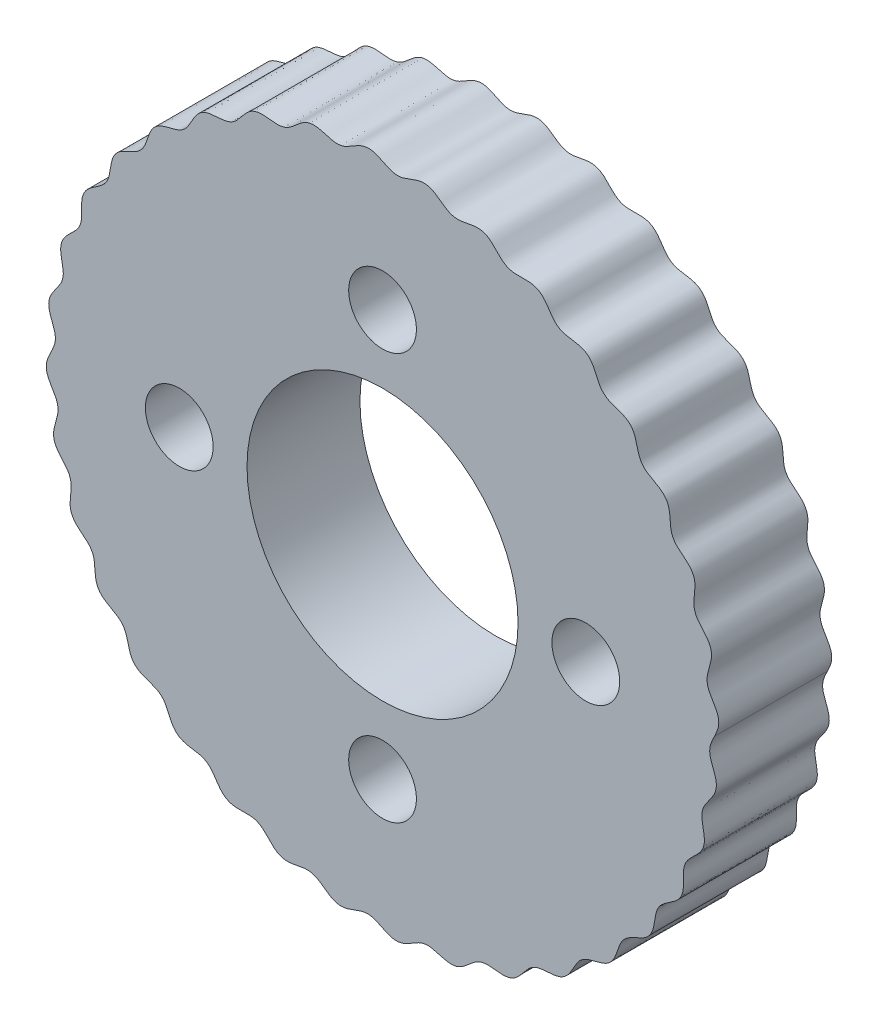
SolidWorks part; units mm, degrees
ref_plane "Front" through (0, 0, 0) normal (0, 0, 1) x (1, 0, 0)
ref_plane "Top" through (0, 0, 0) normal (0, 1, 0) x (1, 0, 0)
ref_plane "Right" through (0, 0, 0) normal (1, 0, 0) x (0, 0, -1)
sketch "草图1" plane through (0, 0, 0) normal (0, 0, 1) x (1, 0, 0)
  circle A0 centre (0, 0) radius 12
  spline S0 degree 4 poles (28.3227, -9.203) (28.4007, -9.0473) (28.5134, -8.7154) (28.521, -8.2566) (28.4217, -7.7169) (28.3239, -7.2476) (28.2639, -6.8452) (28.2638, -6.3709) (28.4238, -5.8514) (28.7631, -5.3537) (29.1643, -4.834) (29.4939, -4.2847) (29.6044, -3.6732) (29.5058, -3.1673) (29.3734, -2.7786) (29.2476, -2.4588) (29.149, -2.2029) (29.0638, -1.9517) (29.0012, -1.7034) (28.9682, -1.4588) (28.9679, -1.2213) (29.0011, -0.9856) (29.0631, -0.7564) (29.1442, -0.5392) (29.2452, -0.3153) (29.3566, -0.0878) (29.4214, 0.0426) (29.5041, 0.2162) (29.5813, 0.3888) (29.6627, 0.5946) (29.7361, 0.8371) (29.7928, 1.1772) (29.7619, 1.5385) (29.6612, 1.8607) (29.5296, 2.143) (29.4093, 2.3613) (29.2811, 2.5748) (29.1513, 2.7874) (29.0136, 3.0244) (28.8805, 3.2922) (28.7417, 3.6812) (28.7105, 4.1623) (28.8201, 4.6646) (28.9806, 5.1874) (29.1102, 5.669) (29.1612, 6.1634) (29.0681, 6.6503) (28.8378, 7.079) (28.5417, 7.4523) (28.2371, 7.7886) (27.9601, 8.1196) (27.7409, 8.4673) (27.607, 8.8339) (27.5577, 9.2505) (27.5832, 9.6969) (27.6437, 10.169) (27.6846, 10.6732) (27.6396, 11.1805) (27.4409, 11.6518) (27.114, 12.0368) (26.734, 12.3591) (26.3695, 12.6411) (26.0523, 12.9227) (25.8058, 13.2224) (25.6414, 13.5328) (25.5328, 13.9054) (25.4814, 14.3267) (25.4592, 14.7869) (25.4154, 15.2832) (25.2947, 15.7655) (25.0405, 16.1911) (24.6776, 16.5153) (24.2715, 16.7647) (23.8703, 16.9765) (23.4969, 17.1929) (23.1719, 17.4446) (22.9207, 17.7433) (22.7319, 18.1179) (22.6032, 18.5461) (22.4985, 19.0105) (22.3646, 19.4982) (22.1488, 19.9595) (21.8008, 20.3344) (21.362, 20.5844) (20.8947, 20.7574) (20.4558, 20.8976) (20.0613, 21.0538) (19.7272, 21.2511) (19.4665, 21.4865) (19.237, 21.7996) (19.0447, 22.1778) (18.8664, 22.6027) (18.6555, 23.0541) (18.3771, 23.466) (17.9927, 23.779) (17.5408, 23.9595) (17.0739, 24.055) (16.6245, 24.1169) (16.1995, 24.1924) (15.8081, 24.3178) (15.4699, 24.5126) (15.1644, 24.8) (14.8969, 25.1584) (14.6397, 25.5589) (14.3471, 25.9715) (13.9865, 26.3312) (13.5313, 26.5645) (13.0334, 26.6493) (12.5351, 26.6519) (12.0747, 26.6336) (11.6507, 26.6454) (11.2692, 26.7166) (10.9437, 26.8487) (10.621, 27.0643) (10.3109, 27.354) (9.998, 27.6922) (9.6455, 28.0444) (9.243, 28.3362) (8.7747, 28.4988) (8.2883, 28.5139) (7.817, 28.4439) (7.3734, 28.3483) (6.9483, 28.274) (6.5375, 28.258) (6.1531, 28.3253) (5.7677, 28.4909) (5.3939, 28.7362) (5.0152, 29.0246) (4.5991, 29.3122) (4.1372, 29.5269) (3.6297, 29.5904) (3.1328, 29.4998) (2.6637, 29.3319) (2.2373, 29.1572) (1.8348, 29.0233) (1.4519, 28.9597) (1.101, 28.9725) (0.7239, 29.0647) (0.3335, 29.2309) (-0.0762, 29.4417) (-0.5279, 29.652) (-1.006, 29.7886) (-1.5017, 29.7812) (-1.9639, 29.629) (-2.3829, 29.4021) (-2.7669, 29.1606) (-3.141, 28.9453) (-3.5215, 28.7898) (-3.9058, 28.7216) (-4.3246, 28.7454) (-4.7598, 28.848) (-5.2143, 28.9895) (-5.7037, 29.1175) (-6.2111, 29.1611) (-6.7098, 29.0473) (-7.1456, 28.7922) (-7.5292, 28.4742) (-7.8698, 28.1637) (-8.2027, 27.901) (-8.6163, 27.6658) (-9.0846, 27.5515) (-9.5983, 27.5723) (-10.141, 27.6395) (-10.6379, 27.6835) (-11.1335, 27.6479) (-11.5969, 27.4717) (-11.9791, 27.1704) (-12.2953, 26.814) (-12.5736, 26.4556) (-12.8515, 26.1254) (-13.1558, 25.8491) (-13.4936, 25.6536) (-13.8953, 25.5327) (-14.3393, 25.4803) (-14.8148, 25.4579) (-15.3184, 25.4107) (-15.8102, 25.2782) (-16.2399, 25.0007) (-16.5622, 24.6119) (-16.8137, 24.1817) (-17.0281, 23.7738) (-17.2503, 23.4125) (-17.5027, 23.1177) (-17.7798, 22.9019) (-18.1279, 22.7302) (-18.5338, 22.6065) (-18.9832, 22.5047) (-19.4644, 22.3754) (-19.9184, 22.1728) (-20.2933, 21.8485) (-20.5496, 21.4348) (-20.7247, 20.9916) (-20.8637, 20.5598) (-21.0118, 20.1544) (-21.2033, 19.7906) (-21.4539, 19.4914) (-21.79, 19.2405) (-22.1893, 19.0393) (-22.6285, 18.8556) (-23.0856, 18.639) (-23.5024, 18.3463) (-23.8112, 17.9386) (-23.9811, 17.463) (-24.0705, 16.9728) (-24.1319, 16.516) (-24.218, 16.1008) (-24.3837, 15.6548) (-24.669, 15.2662) (-25.0758, 14.9519) (-25.5348, 14.6546) (-25.9437, 14.3689) (-26.3005, 14.023) (-26.5422, 13.5902) (-26.6414, 13.1137) (-26.6544, 12.6374) (-26.6373, 12.184) (-26.6379, 11.7525) (-26.6934, 11.3451) (-26.8265, 10.9783) (-27.0565, 10.6275) (-27.363, 10.3019) (-27.7128, 9.9791) (-28.0683, 9.6192) (-28.3598, 9.2016) (-28.5106, 8.7128) (-28.5076, 8.2078) (-28.4239, 7.7167) (-28.3254, 7.2664) (-28.2643, 6.8468) (-28.2674, 6.371) (-28.4026, 5.9083) (-28.6774, 5.4737) (-29.0071, 5.0374) (-29.2934, 4.6291) (-29.5189, 4.1654) (-29.596, 3.6363) (-29.5072, 3.1705) (-29.3741, 2.7812) (-29.2486, 2.4612) (-29.1621, 2.237) (-29.0944, 2.0423) (-29.039, 1.8536) (-28.9969, 1.671) (-28.9683, 1.4602) (-28.9678, 1.2226) (-29.0008, 0.9866) (-29.0628, 0.7571) (-29.144, 0.5397) (-29.2451, 0.3156) (-29.3565, 0.088) (-29.4213, -0.0425) (-29.504, -0.216) (-29.5811, -0.3884) (-29.6625, -0.594) (-29.7359, -0.8363) (-29.7927, -1.1758) (-29.7569, -1.5999) (-29.5968, -2.0358) (-29.3501, -2.468) (-29.104, -2.8573) (-28.9029, -3.23) (-28.7425, -3.6775) (-28.7102, -4.158) (-28.8184, -4.6601) (-28.9796, -5.1824) (-29.108, -5.6634) (-29.1694, -6.219) (-29.0205, -6.8287) (-28.6698, -7.3074) (-28.2995, -7.7184) (-27.9914, -8.0807) (-27.773, -8.4064) (-27.66, -8.6803) (-27.6148, -8.8706) (-27.5993, -8.9677) knots 0 0 0 0 0 0.005917 0.011834 0.015307 0.01878 0.022253 0.025726 0.031361 0.036997 0.042632 0.048268 0.052952 0.057637 0.059979 0.062321 0.064663 0.067005 0.069026 0.071047 0.073068 0.075089 0.07711 0.079131 0.081152 0.083173 0.084644 0.086115 0.087586 0.089057 0.091999 0.094941 0.099192 0.101318 0.103443 0.105569 0.107694 0.10982 0.111945 0.11492 0.117895 0.123845 0.128096 0.132347 0.136598 0.140849 0.14491 0.148972 0.153034 0.157095 0.160395 0.163694 0.166994 0.170293 0.174609 0.178924 0.18324 0.187556 0.191807 0.196057 0.200308 0.204559 0.207534 0.210509 0.213484 0.216459 0.22071 0.224961 0.229212 0.233463 0.237525 0.241586 0.245648 0.24971 0.253009 0.256309 0.259608 0.262908 0.267223 0.271539 0.275854 0.28017 0.284421 0.288672 0.292923 0.297174 0.300149 0.303124 0.306099 0.309073 0.313324 0.317575 0.321826 0.326077 0.330139 0.334201 0.338262 0.342324 0.345623 0.348923 0.352222 0.355522 0.359838 0.364153 0.368469 0.372784 0.377035 0.381286 0.385537 0.389788 0.392763 0.395738 0.398713 0.401688 0.405939 0.41019 0.414441 0.418692 0.422753 0.426815 0.430877 0.434938 0.438238 0.441537 0.444837 0.448136 0.452452 0.456768 0.461083 0.465399 0.46965 0.473901 0.478152 0.482403 0.485378 0.488352 0.491327 0.494302 0.498553 0.502804 0.507055 0.511306 0.515368 0.519429 0.523491 0.527553 0.530852 0.534152 0.537451 0.540751 0.545066 0.549382 0.553698 0.558013 0.562264 0.566515 0.570766 0.575017 0.577992 0.580967 0.586917 0.591168 0.595419 0.59967 0.60392 0.607982 0.612044 0.616105 0.620167 0.623467 0.626766 0.630066 0.633365 0.637681 0.641996 0.646312 0.650628 0.654878 0.659129 0.66338 0.667631 0.670606 0.673581 0.676556 0.679531 0.683782 0.688033 0.692284 0.696535 0.700597 0.704658 0.70872 0.712782 0.716081 0.71938 0.72268 0.725979 0.730295 0.734611 0.738926 0.743242 0.747493 0.751744 0.755995 0.760246 0.763221 0.766196 0.772145 0.776396 0.780647 0.784898 0.789149 0.793211 0.797273 0.801334 0.805396 0.808695 0.811995 0.815294 0.818594 0.822909 0.827225 0.831541 0.835856 0.840107 0.844358 0.848609 0.85286 0.855835 0.85881 0.86476 0.869011 0.873262 0.877513 0.881764 0.886453 0.891141 0.893486 0.89583 0.898175 0.899347 0.900519 0.902542 0.904565 0.906588 0.908611 0.910634 0.912657 0.91468 0.916703 0.918172 0.919642 0.921111 0.922581 0.92552 0.928459 0.932706 0.936953 0.9412 0.945447 0.948419 0.951391 0.957335 0.961582 0.965829 0.970076 0.974323 0.980485 0.986648 0.989986 0.993324 0.996662 1 1 1 1 1 construction
  spline S1 degree 4 poles (29.4, 0) (29.4158, 0.0323) (29.4474, 0.0972) (29.5041, 0.2162) (29.5813, 0.3888) (29.6627, 0.5946) (29.7361, 0.8371) (29.7928, 1.1772) (29.7619, 1.5385) (29.6612, 1.8607) (29.5296, 2.143) (29.4093, 2.3613) (29.2811, 2.5748) (29.1513, 2.7874) (29.0136, 3.0244) (28.8805, 3.2922) (28.7417, 3.6812) (28.7105, 4.1623) (28.8201, 4.6646) (28.9806, 5.1874) (29.1102, 5.669) (29.1612, 6.1634) (29.0681, 6.6503) (28.8378, 7.079) (28.5417, 7.4523) (28.2371, 7.7886) (27.9601, 8.1196) (27.7409, 8.4673) (27.607, 8.8339) (27.5577, 9.2505) (27.5832, 9.6969) (27.6437, 10.169) (27.6846, 10.6732) (27.6396, 11.1805) (27.4409, 11.6518) (27.114, 12.0368) (26.734, 12.3591) (26.3695, 12.6411) (26.0523, 12.9227) (25.8058, 13.2224) (25.6414, 13.5328) (25.5328, 13.9054) (25.4814, 14.3267) (25.4592, 14.7869) (25.4154, 15.2832) (25.2947, 15.7655) (25.0405, 16.1911) (24.6776, 16.5153) (24.2715, 16.7647) (23.8703, 16.9765) (23.4969, 17.1929) (23.1719, 17.4446) (22.9207, 17.7433) (22.7319, 18.1179) (22.6032, 18.5461) (22.4985, 19.0105) (22.3646, 19.4982) (22.1488, 19.9595) (21.8008, 20.3344) (21.362, 20.5844) (20.8947, 20.7574) (20.4558, 20.8976) (20.0613, 21.0538) (19.7272, 21.2511) (19.4665, 21.4865) (19.237, 21.7996) (19.0447, 22.1778) (18.8664, 22.6027) (18.6555, 23.0541) (18.3771, 23.466) (17.9927, 23.779) (17.5408, 23.9595) (17.0739, 24.055) (16.6245, 24.1169) (16.1995, 24.1924) (15.8081, 24.3178) (15.4699, 24.5126) (15.1644, 24.8) (14.8969, 25.1584) (14.6397, 25.5589) (14.3471, 25.9715) (13.9865, 26.3312) (13.5313, 26.5645) (13.0334, 26.6493) (12.5351, 26.6519) (12.0747, 26.6336) (11.6507, 26.6454) (11.2692, 26.7166) (10.9437, 26.8487) (10.621, 27.0643) (10.3109, 27.354) (9.998, 27.6922) (9.6455, 28.0444) (9.243, 28.3362) (8.7747, 28.4988) (8.2883, 28.5139) (7.817, 28.4439) (7.3734, 28.3483) (6.9483, 28.274) (6.5375, 28.258) (6.1531, 28.3253) (5.7677, 28.4909) (5.3939, 28.7362) (5.0152, 29.0246) (4.5991, 29.3122) (4.1372, 29.5269) (3.6297, 29.5904) (3.1328, 29.4998) (2.6637, 29.3319) (2.2373, 29.1572) (1.8348, 29.0233) (1.4519, 28.9597) (1.101, 28.9725) (0.7239, 29.0647) (0.3335, 29.2309) (-0.0762, 29.4417) (-0.5279, 29.652) (-1.006, 29.7886) (-1.5017, 29.7812) (-1.9639, 29.629) (-2.3829, 29.4021) (-2.7669, 29.1606) (-3.141, 28.9453) (-3.5215, 28.7898) (-3.9058, 28.7216) (-4.3246, 28.7454) (-4.7598, 28.848) (-5.2143, 28.9895) (-5.7037, 29.1175) (-6.2111, 29.1611) (-6.7098, 29.0473) (-7.1456, 28.7922) (-7.5292, 28.4742) (-7.8698, 28.1637) (-8.2027, 27.901) (-8.6163, 27.6658) (-9.0846, 27.5515) (-9.5983, 27.5723) (-10.141, 27.6395) (-10.6379, 27.6835) (-11.1335, 27.6479) (-11.5969, 27.4717) (-11.9791, 27.1704) (-12.2953, 26.814) (-12.5736, 26.4556) (-12.8515, 26.1254) (-13.1558, 25.8491) (-13.4936, 25.6536) (-13.8953, 25.5327) (-14.3393, 25.4803) (-14.8148, 25.4579) (-15.3184, 25.4107) (-15.8102, 25.2782) (-16.2399, 25.0007) (-16.5622, 24.6119) (-16.8137, 24.1817) (-17.0281, 23.7738) (-17.2503, 23.4125) (-17.5027, 23.1177) (-17.7798, 22.9019) (-18.1279, 22.7302) (-18.5338, 22.6065) (-18.9832, 22.5047) (-19.4644, 22.3754) (-19.9184, 22.1728) (-20.2933, 21.8485) (-20.5496, 21.4348) (-20.7247, 20.9916) (-20.8637, 20.5598) (-21.0118, 20.1544) (-21.2033, 19.7906) (-21.4539, 19.4914) (-21.79, 19.2405) (-22.1893, 19.0393) (-22.6285, 18.8556) (-23.0856, 18.639) (-23.5024, 18.3463) (-23.8112, 17.9386) (-23.9811, 17.463) (-24.0705, 16.9728) (-24.1319, 16.516) (-24.218, 16.1008) (-24.3837, 15.6548) (-24.669, 15.2662) (-25.0758, 14.9519) (-25.5348, 14.6546) (-25.9437, 14.3689) (-26.3005, 14.023) (-26.5422, 13.5902) (-26.6414, 13.1137) (-26.6544, 12.6374) (-26.6373, 12.184) (-26.6379, 11.7525) (-26.6934, 11.3451) (-26.8265, 10.9783) (-27.0565, 10.6275) (-27.363, 10.3019) (-27.7128, 9.9791) (-28.0683, 9.6192) (-28.3598, 9.2016) (-28.5106, 8.7128) (-28.5076, 8.2078) (-28.4239, 7.7167) (-28.3254, 7.2664) (-28.2643, 6.8468) (-28.2674, 6.371) (-28.4026, 5.9083) (-28.6774, 5.4737) (-29.0071, 5.0374) (-29.2934, 4.6291) (-29.5189, 4.1654) (-29.596, 3.6363) (-29.5072, 3.1705) (-29.3741, 2.7812) (-29.2486, 2.4612) (-29.1621, 2.237) (-29.0944, 2.0423) (-29.039, 1.8536) (-28.9969, 1.671) (-28.9683, 1.4602) (-28.9678, 1.2226) (-29.0008, 0.9866) (-29.0628, 0.7571) (-29.144, 0.5397) (-29.2451, 0.3156) (-29.3348, 0.1323) (-29.3783, 0.0444) (-29.4, 0) knots 0.083173 0.083173 0.083173 0.083173 0.083173 0.084644 0.086115 0.087586 0.089057 0.091999 0.094941 0.099192 0.101318 0.103443 0.105569 0.107694 0.10982 0.111945 0.11492 0.117895 0.123845 0.128096 0.132347 0.136598 0.140849 0.14491 0.148972 0.153034 0.157095 0.160395 0.163694 0.166994 0.170293 0.174609 0.178924 0.18324 0.187556 0.191807 0.196057 0.200308 0.204559 0.207534 0.210509 0.213484 0.216459 0.22071 0.224961 0.229212 0.233463 0.237525 0.241586 0.245648 0.24971 0.253009 0.256309 0.259608 0.262908 0.267223 0.271539 0.275854 0.28017 0.284421 0.288672 0.292923 0.297174 0.300149 0.303124 0.306099 0.309073 0.313324 0.317575 0.321826 0.326077 0.330139 0.334201 0.338262 0.342324 0.345623 0.348923 0.352222 0.355522 0.359838 0.364153 0.368469 0.372784 0.377035 0.381286 0.385537 0.389788 0.392763 0.395738 0.398713 0.401688 0.405939 0.41019 0.414441 0.418692 0.422753 0.426815 0.430877 0.434938 0.438238 0.441537 0.444837 0.448136 0.452452 0.456768 0.461083 0.465399 0.46965 0.473901 0.478152 0.482403 0.485378 0.488352 0.491327 0.494302 0.498553 0.502804 0.507055 0.511306 0.515368 0.519429 0.523491 0.527553 0.530852 0.534152 0.537451 0.540751 0.545066 0.549382 0.553698 0.558013 0.562264 0.566515 0.570766 0.575017 0.577992 0.580967 0.586917 0.591168 0.595419 0.59967 0.60392 0.607982 0.612044 0.616105 0.620167 0.623467 0.626766 0.630066 0.633365 0.637681 0.641996 0.646312 0.650628 0.654878 0.659129 0.66338 0.667631 0.670606 0.673581 0.676556 0.679531 0.683782 0.688033 0.692284 0.696535 0.700597 0.704658 0.70872 0.712782 0.716081 0.71938 0.72268 0.725979 0.730295 0.734611 0.738926 0.743242 0.747493 0.751744 0.755995 0.760246 0.763221 0.766196 0.772145 0.776396 0.780647 0.784898 0.789149 0.793211 0.797273 0.801334 0.805396 0.808695 0.811995 0.815294 0.818594 0.822909 0.827225 0.831541 0.835856 0.840107 0.844358 0.848609 0.85286 0.855835 0.85881 0.86476 0.869011 0.873262 0.877513 0.881764 0.886453 0.891141 0.893486 0.89583 0.898175 0.899347 0.900519 0.902542 0.904565 0.906588 0.908611 0.910634 0.912657 0.91468 0.916703 0.916703 0.916703 0.916703 0.916703
  spline S2 degree 4 poles (-28.3227, 9.203) (-28.4007, 9.0473) (-28.5134, 8.7154) (-28.521, 8.2566) (-28.4217, 7.7169) (-28.3239, 7.2476) (-28.2639, 6.8452) (-28.2638, 6.3709) (-28.4238, 5.8514) (-28.7631, 5.3537) (-29.1643, 4.834) (-29.4939, 4.2847) (-29.6044, 3.6732) (-29.5058, 3.1673) (-29.3734, 2.7786) (-29.2476, 2.4588) (-29.149, 2.2029) (-29.0638, 1.9517) (-29.0012, 1.7034) (-28.9682, 1.4588) (-28.9679, 1.2213) (-29.0011, 0.9856) (-29.0631, 0.7564) (-29.1442, 0.5392) (-29.2452, 0.3153) (-29.3566, 0.0878) (-29.4214, -0.0426) (-29.5041, -0.2162) (-29.5813, -0.3888) (-29.6627, -0.5946) (-29.7362, -0.8371) (-29.7928, -1.177) (-29.7565, -1.6014) (-29.5959, -2.0377) (-29.3488, -2.4701) (-29.1025, -2.8598) (-28.9014, -3.2331) (-28.7418, -3.6813) (-28.7104, -4.1623) (-28.8201, -4.6646) (-28.9806, -5.1874) (-29.1102, -5.669) (-29.1612, -6.1634) (-29.0681, -6.6503) (-28.8378, -7.079) (-28.5417, -7.4523) (-28.2371, -7.7886) (-27.9601, -8.1196) (-27.7409, -8.4673) (-27.607, -8.8339) (-27.5577, -9.2505) (-27.5832, -9.6969) (-27.6437, -10.169) (-27.6846, -10.6732) (-27.6396, -11.1805) (-27.4409, -11.6518) (-27.114, -12.0368) (-26.734, -12.3591) (-26.3695, -12.6411) (-26.0523, -12.9227) (-25.8058, -13.2224) (-25.6414, -13.5328) (-25.5328, -13.9054) (-25.4814, -14.3267) (-25.4592, -14.7869) (-25.4154, -15.2832) (-25.2947, -15.7655) (-25.0405, -16.1911) (-24.6776, -16.5153) (-24.2715, -16.7647) (-23.8703, -16.9765) (-23.4969, -17.1929) (-23.1719, -17.4446) (-22.9207, -17.7433) (-22.7319, -18.1179) (-22.6032, -18.5461) (-22.4985, -19.0105) (-22.3646, -19.4982) (-22.1488, -19.9595) (-21.8008, -20.3344) (-21.362, -20.5844) (-20.8947, -20.7574) (-20.4558, -20.8976) (-20.0613, -21.0538) (-19.7272, -21.2511) (-19.4665, -21.4865) (-19.237, -21.7996) (-19.0447, -22.1778) (-18.8664, -22.6027) (-18.6555, -23.0541) (-18.3771, -23.466) (-17.9927, -23.779) (-17.5408, -23.9595) (-17.0739, -24.055) (-16.6245, -24.1169) (-16.1995, -24.1924) (-15.8081, -24.3178) (-15.4699, -24.5126) (-15.1644, -24.8) (-14.8969, -25.1584) (-14.6397, -25.5589) (-14.3471, -25.9715) (-13.9865, -26.3312) (-13.5313, -26.5645) (-13.0334, -26.6493) (-12.5351, -26.6519) (-12.0747, -26.6336) (-11.6507, -26.6454) (-11.2692, -26.7166) (-10.9437, -26.8487) (-10.621, -27.0643) (-10.3109, -27.354) (-9.998, -27.6922) (-9.6455, -28.0444) (-9.243, -28.3362) (-8.7747, -28.4988) (-8.2883, -28.5139) (-7.817, -28.4439) (-7.3734, -28.3483) (-6.9483, -28.274) (-6.5375, -28.258) (-6.1531, -28.3253) (-5.7677, -28.4909) (-5.3939, -28.7362) (-5.0152, -29.0246) (-4.5991, -29.3122) (-4.1372, -29.5269) (-3.6297, -29.5904) (-3.1328, -29.4998) (-2.6637, -29.3319) (-2.2373, -29.1572) (-1.8348, -29.0233) (-1.4519, -28.9597) (-1.101, -28.9725) (-0.7239, -29.0647) (-0.3335, -29.2309) (0.0762, -29.4417) (0.5279, -29.652) (1.006, -29.7886) (1.5017, -29.7812) (1.9639, -29.629) (2.3829, -29.4021) (2.7669, -29.1606) (3.141, -28.9453) (3.5215, -28.7898) (3.9058, -28.7216) (4.3246, -28.7454) (4.7598, -28.848) (5.2143, -28.9895) (5.7037, -29.1174) (6.2111, -29.1612) (6.7097, -29.0473) (7.1456, -28.7923) (7.5291, -28.474) (7.87, -28.164) (8.2024, -27.9005) (8.5404, -27.7098) (8.8746, -27.6018) (9.2605, -27.5595) (9.6842, -27.5821) (10.1413, -27.6401) (10.6377, -27.6832) (11.1336, -27.6481) (11.5969, -27.4716) (11.9792, -27.1705) (12.2953, -26.8139) (12.5736, -26.4556) (12.8515, -26.1254) (13.1558, -25.8491) (13.4936, -25.6536) (13.8953, -25.5327) (14.3393, -25.4803) (14.8148, -25.4579) (15.3184, -25.4107) (15.8102, -25.2782) (16.2399, -25.0007) (16.5622, -24.6119) (16.8137, -24.1817) (17.0281, -23.7738) (17.2503, -23.4125) (17.5027, -23.1177) (17.7798, -22.9019) (18.1279, -22.7302) (18.5338, -22.6065) (18.9832, -22.5047) (19.4644, -22.3754) (19.9184, -22.1728) (20.2933, -21.8485) (20.5496, -21.4348) (20.7247, -20.9916) (20.8637, -20.5598) (21.0118, -20.1544) (21.2033, -19.7906) (21.4539, -19.4914) (21.79, -19.2405) (22.1893, -19.0393) (22.6285, -18.8556) (23.0856, -18.639) (23.5024, -18.3463) (23.8112, -17.9386) (23.9812, -17.463) (24.0703, -16.9728) (24.1323, -16.5161) (24.2175, -16.1006) (24.3539, -15.7373) (24.5404, -15.4397) (24.8088, -15.1593) (25.148, -14.9042) (25.5354, -14.6548) (25.9434, -14.3688) (26.3007, -14.0231) (26.5421, -13.5901) (26.6414, -13.1137) (26.6544, -12.6374) (26.6373, -12.1841) (26.6379, -11.7525) (26.6934, -11.3451) (26.8265, -10.9783) (27.0565, -10.6275) (27.363, -10.3019) (27.7128, -9.9791) (28.0683, -9.6192) (28.3599, -9.2016) (28.5106, -8.7128) (28.5077, -8.2078) (28.4237, -7.7166) (28.3258, -7.2664) (28.2638, -6.8467) (28.2676, -6.4587) (28.3411, -6.1153) (28.4975, -5.76) (28.7289, -5.4043) (29.0078, -5.0375) (29.2931, -4.629) (29.5191, -4.1654) (29.5958, -3.6363) (29.5073, -3.1705) (29.3741, -2.7812) (29.2487, -2.4612) (29.1621, -2.237) (29.0944, -2.0423) (29.039, -1.8536) (28.9969, -1.671) (28.9683, -1.4602) (28.9678, -1.2226) (29.0008, -0.9866) (29.0628, -0.7571) (29.144, -0.5397) (29.2451, -0.3156) (29.3565, -0.088) (29.4213, 0.0425) (29.504, 0.216) (29.5811, 0.3884) (29.6625, 0.594) (29.7359, 0.8363) (29.7927, 1.1758) (29.7569, 1.5999) (29.5968, 2.0358) (29.3501, 2.468) (29.104, 2.8573) (28.9029, 3.23) (28.7425, 3.6775) (28.7102, 4.158) (28.8184, 4.6601) (28.9796, 5.1824) (29.108, 5.6634) (29.1694, 6.219) (29.0205, 6.8287) (28.6698, 7.3074) (28.2995, 7.7184) (27.9914, 8.0807) (27.773, 8.4064) (27.66, 8.6803) (27.6148, 8.8706) (27.5993, 8.9677) knots 0 0 0 0 0 0.005917 0.011834 0.015307 0.01878 0.022253 0.025726 0.031361 0.036997 0.042632 0.048268 0.052952 0.057637 0.059979 0.062321 0.064663 0.067005 0.069026 0.071047 0.073068 0.075089 0.07711 0.079131 0.081152 0.083173 0.084644 0.086115 0.087586 0.089057 0.091999 0.094941 0.099192 0.103443 0.107694 0.111945 0.11492 0.117895 0.123845 0.128096 0.132347 0.136598 0.140849 0.14491 0.148972 0.153034 0.157095 0.160395 0.163694 0.166994 0.170293 0.174609 0.178924 0.18324 0.187556 0.191807 0.196057 0.200308 0.204559 0.207534 0.210509 0.213484 0.216459 0.22071 0.224961 0.229212 0.233463 0.237525 0.241586 0.245648 0.24971 0.253009 0.256309 0.259608 0.262908 0.267223 0.271539 0.275854 0.28017 0.284421 0.288672 0.292923 0.297174 0.300149 0.303124 0.306099 0.309073 0.313324 0.317575 0.321826 0.326077 0.330139 0.334201 0.338262 0.342324 0.345623 0.348923 0.352222 0.355522 0.359838 0.364153 0.368469 0.372784 0.377035 0.381286 0.385537 0.389788 0.392763 0.395738 0.398713 0.401688 0.405939 0.41019 0.414441 0.418692 0.422753 0.426815 0.430877 0.434938 0.438238 0.441537 0.444837 0.448136 0.452452 0.456768 0.461083 0.465399 0.46965 0.473901 0.478152 0.482403 0.485378 0.488352 0.491327 0.494302 0.498553 0.502804 0.507055 0.511306 0.515368 0.519429 0.523491 0.527553 0.530852 0.534152 0.537451 0.540751 0.545066 0.549382 0.553698 0.558013 0.562264 0.566515 0.570766 0.575017 0.577992 0.580967 0.583942 0.586917 0.591168 0.595419 0.59967 0.60392 0.607982 0.612044 0.616105 0.620167 0.623467 0.626766 0.630066 0.633365 0.637681 0.641996 0.646312 0.650628 0.654878 0.659129 0.66338 0.667631 0.670606 0.673581 0.676556 0.679531 0.683782 0.688033 0.692284 0.696535 0.700597 0.704658 0.70872 0.712782 0.716081 0.71938 0.72268 0.725979 0.730295 0.734611 0.738926 0.743242 0.747493 0.751744 0.755995 0.760246 0.763221 0.766196 0.769171 0.772145 0.776396 0.780647 0.784898 0.789149 0.793211 0.797273 0.801334 0.805396 0.808695 0.811995 0.815294 0.818594 0.822909 0.827225 0.831541 0.835856 0.840107 0.844358 0.848609 0.85286 0.855835 0.85881 0.861785 0.86476 0.869011 0.873262 0.877513 0.881764 0.886453 0.891141 0.893486 0.89583 0.898175 0.899347 0.900519 0.902542 0.904565 0.906588 0.908611 0.910634 0.912657 0.91468 0.916703 0.918172 0.919642 0.921111 0.922581 0.92552 0.928459 0.932706 0.936953 0.9412 0.945447 0.948419 0.951391 0.957335 0.961582 0.965829 0.970076 0.974323 0.980485 0.986648 0.989986 0.993324 0.996662 1 1 1 1 1 construction
  spline S3 degree 4 poles (-29.4, 0) (-29.4158, -0.0323) (-29.4474, -0.0972) (-29.5041, -0.2162) (-29.5813, -0.3888) (-29.6627, -0.5946) (-29.7362, -0.8371) (-29.7928, -1.177) (-29.7565, -1.6014) (-29.5959, -2.0377) (-29.3488, -2.4701) (-29.1025, -2.8598) (-28.9014, -3.2331) (-28.7418, -3.6813) (-28.7104, -4.1623) (-28.8201, -4.6646) (-28.9806, -5.1874) (-29.1102, -5.669) (-29.1612, -6.1634) (-29.0681, -6.6503) (-28.8378, -7.079) (-28.5417, -7.4523) (-28.2371, -7.7886) (-27.9601, -8.1196) (-27.7409, -8.4673) (-27.607, -8.8339) (-27.5577, -9.2505) (-27.5832, -9.6969) (-27.6437, -10.169) (-27.6846, -10.6732) (-27.6396, -11.1805) (-27.4409, -11.6518) (-27.114, -12.0368) (-26.734, -12.3591) (-26.3695, -12.6411) (-26.0523, -12.9227) (-25.8058, -13.2224) (-25.6414, -13.5328) (-25.5328, -13.9054) (-25.4814, -14.3267) (-25.4592, -14.7869) (-25.4154, -15.2832) (-25.2947, -15.7655) (-25.0405, -16.1911) (-24.6776, -16.5153) (-24.2715, -16.7647) (-23.8703, -16.9765) (-23.4969, -17.1929) (-23.1719, -17.4446) (-22.9207, -17.7433) (-22.7319, -18.1179) (-22.6032, -18.5461) (-22.4985, -19.0105) (-22.3646, -19.4982) (-22.1488, -19.9595) (-21.8008, -20.3344) (-21.362, -20.5844) (-20.8947, -20.7574) (-20.4558, -20.8976) (-20.0613, -21.0538) (-19.7272, -21.2511) (-19.4665, -21.4865) (-19.237, -21.7996) (-19.0447, -22.1778) (-18.8664, -22.6027) (-18.6555, -23.0541) (-18.3771, -23.466) (-17.9927, -23.779) (-17.5408, -23.9595) (-17.0739, -24.055) (-16.6245, -24.1169) (-16.1995, -24.1924) (-15.8081, -24.3178) (-15.4699, -24.5126) (-15.1644, -24.8) (-14.8969, -25.1584) (-14.6397, -25.5589) (-14.3471, -25.9715) (-13.9865, -26.3312) (-13.5313, -26.5645) (-13.0334, -26.6493) (-12.5351, -26.6519) (-12.0747, -26.6336) (-11.6507, -26.6454) (-11.2692, -26.7166) (-10.9437, -26.8487) (-10.621, -27.0643) (-10.3109, -27.354) (-9.998, -27.6922) (-9.6455, -28.0444) (-9.243, -28.3362) (-8.7747, -28.4988) (-8.2883, -28.5139) (-7.817, -28.4439) (-7.3734, -28.3483) (-6.9483, -28.274) (-6.5375, -28.258) (-6.1531, -28.3253) (-5.7677, -28.4909) (-5.3939, -28.7362) (-5.0152, -29.0246) (-4.5991, -29.3122) (-4.1372, -29.5269) (-3.6297, -29.5904) (-3.1328, -29.4998) (-2.6637, -29.3319) (-2.2373, -29.1572) (-1.8348, -29.0233) (-1.4519, -28.9597) (-1.101, -28.9725) (-0.7239, -29.0647) (-0.3335, -29.2309) (0.0762, -29.4417) (0.5279, -29.652) (1.006, -29.7886) (1.5017, -29.7812) (1.9639, -29.629) (2.3829, -29.4021) (2.7669, -29.1606) (3.141, -28.9453) (3.5215, -28.7898) (3.9058, -28.7216) (4.3246, -28.7454) (4.7598, -28.848) (5.2143, -28.9895) (5.7037, -29.1174) (6.2111, -29.1612) (6.7097, -29.0473) (7.1456, -28.7923) (7.5291, -28.474) (7.87, -28.164) (8.2024, -27.9005) (8.5404, -27.7098) (8.8746, -27.6018) (9.2605, -27.5595) (9.6842, -27.5821) (10.1413, -27.6401) (10.6377, -27.6832) (11.1336, -27.6481) (11.5969, -27.4716) (11.9792, -27.1705) (12.2953, -26.8139) (12.5736, -26.4556) (12.8515, -26.1254) (13.1558, -25.8491) (13.4936, -25.6536) (13.8953, -25.5327) (14.3393, -25.4803) (14.8148, -25.4579) (15.3184, -25.4107) (15.8102, -25.2782) (16.2399, -25.0007) (16.5622, -24.6119) (16.8137, -24.1817) (17.0281, -23.7738) (17.2503, -23.4125) (17.5027, -23.1177) (17.7798, -22.9019) (18.1279, -22.7302) (18.5338, -22.6065) (18.9832, -22.5047) (19.4644, -22.3754) (19.9184, -22.1728) (20.2933, -21.8485) (20.5496, -21.4348) (20.7247, -20.9916) (20.8637, -20.5598) (21.0118, -20.1544) (21.2033, -19.7906) (21.4539, -19.4914) (21.79, -19.2405) (22.1893, -19.0393) (22.6285, -18.8556) (23.0856, -18.639) (23.5024, -18.3463) (23.8112, -17.9386) (23.9812, -17.463) (24.0703, -16.9728) (24.1323, -16.5161) (24.2175, -16.1006) (24.3539, -15.7373) (24.5404, -15.4397) (24.8088, -15.1593) (25.148, -14.9042) (25.5354, -14.6548) (25.9434, -14.3688) (26.3007, -14.0231) (26.5421, -13.5901) (26.6414, -13.1137) (26.6544, -12.6374) (26.6373, -12.1841) (26.6379, -11.7525) (26.6934, -11.3451) (26.8265, -10.9783) (27.0565, -10.6275) (27.363, -10.3019) (27.7128, -9.9791) (28.0683, -9.6192) (28.3599, -9.2016) (28.5106, -8.7128) (28.5077, -8.2078) (28.4237, -7.7166) (28.3258, -7.2664) (28.2638, -6.8467) (28.2676, -6.4587) (28.3411, -6.1153) (28.4975, -5.76) (28.7289, -5.4043) (29.0078, -5.0375) (29.2931, -4.629) (29.5191, -4.1654) (29.5958, -3.6363) (29.5073, -3.1705) (29.3741, -2.7812) (29.2487, -2.4612) (29.1621, -2.237) (29.0944, -2.0423) (29.039, -1.8536) (28.9969, -1.671) (28.9683, -1.4602) (28.9678, -1.2226) (29.0008, -0.9866) (29.0628, -0.7571) (29.144, -0.5397) (29.2451, -0.3156) (29.3348, -0.1323) (29.3783, -0.0444) (29.4, 0) knots 0.083173 0.083173 0.083173 0.083173 0.083173 0.084644 0.086115 0.087586 0.089057 0.091999 0.094941 0.099192 0.103443 0.107694 0.111945 0.11492 0.117895 0.123845 0.128096 0.132347 0.136598 0.140849 0.14491 0.148972 0.153034 0.157095 0.160395 0.163694 0.166994 0.170293 0.174609 0.178924 0.18324 0.187556 0.191807 0.196057 0.200308 0.204559 0.207534 0.210509 0.213484 0.216459 0.22071 0.224961 0.229212 0.233463 0.237525 0.241586 0.245648 0.24971 0.253009 0.256309 0.259608 0.262908 0.267223 0.271539 0.275854 0.28017 0.284421 0.288672 0.292923 0.297174 0.300149 0.303124 0.306099 0.309073 0.313324 0.317575 0.321826 0.326077 0.330139 0.334201 0.338262 0.342324 0.345623 0.348923 0.352222 0.355522 0.359838 0.364153 0.368469 0.372784 0.377035 0.381286 0.385537 0.389788 0.392763 0.395738 0.398713 0.401688 0.405939 0.41019 0.414441 0.418692 0.422753 0.426815 0.430877 0.434938 0.438238 0.441537 0.444837 0.448136 0.452452 0.456768 0.461083 0.465399 0.46965 0.473901 0.478152 0.482403 0.485378 0.488352 0.491327 0.494302 0.498553 0.502804 0.507055 0.511306 0.515368 0.519429 0.523491 0.527553 0.530852 0.534152 0.537451 0.540751 0.545066 0.549382 0.553698 0.558013 0.562264 0.566515 0.570766 0.575017 0.577992 0.580967 0.583942 0.586917 0.591168 0.595419 0.59967 0.60392 0.607982 0.612044 0.616105 0.620167 0.623467 0.626766 0.630066 0.633365 0.637681 0.641996 0.646312 0.650628 0.654878 0.659129 0.66338 0.667631 0.670606 0.673581 0.676556 0.679531 0.683782 0.688033 0.692284 0.696535 0.700597 0.704658 0.70872 0.712782 0.716081 0.71938 0.72268 0.725979 0.730295 0.734611 0.738926 0.743242 0.747493 0.751744 0.755995 0.760246 0.763221 0.766196 0.769171 0.772145 0.776396 0.780647 0.784898 0.789149 0.793211 0.797273 0.801334 0.805396 0.808695 0.811995 0.815294 0.818594 0.822909 0.827225 0.831541 0.835856 0.840107 0.844358 0.848609 0.85286 0.855835 0.85881 0.861785 0.86476 0.869011 0.873262 0.877513 0.881764 0.886453 0.891141 0.893486 0.89583 0.898175 0.899347 0.900519 0.902542 0.904565 0.906588 0.908611 0.910634 0.912657 0.91468 0.916703 0.916703 0.916703 0.916703 0.916703
extrude "凸台-拉伸1" add sketch "草图1" along normal blind 5 and the other way blind 5
sketch "草图2" plane through (0, 0, 0) normal (0, 0, 1) x (1, 0, 0)
  circle A1 centre (18, 0) radius 3
  circle A2 centre (0, -18) radius 3
  circle A3 centre (-18, 0) radius 3
  circle A4 centre (0, 18) radius 3
  point P12 (0, 0)
  dimension "D1" = 4
extrude "切除-拉伸1" cut sketch "草图2" against normal blind 10 and the other way blind 10
